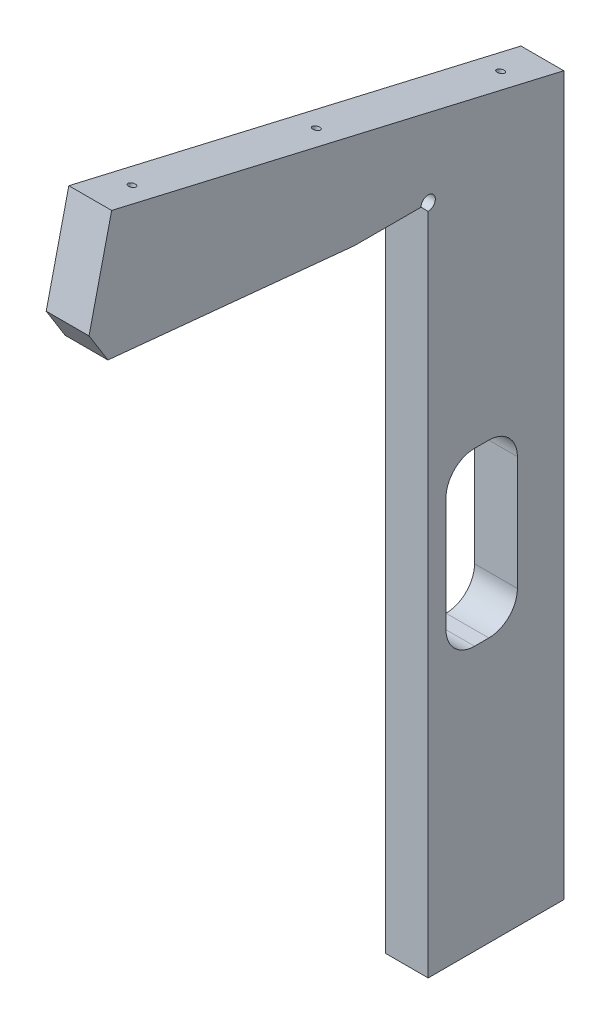
SolidWorks part; units mm, degrees
material "MDF"
ref_plane "Front Plane" through (0, 0, 0) normal (0, 0, 1) x (1, 0, 0)
ref_plane "Top Plane" through (0, 0, 0) normal (0, 1, 0) x (1, 0, 0)
ref_plane "Right Plane" through (0, 0, 0) normal (1, 0, 0) x (0, 0, -1)
sketch "Sketch2" plane through (-113.7888, 0, 0) normal (1, 0, 0) x (0, 0, -1)
  line L17 (0, 20.8246) -> (-83.8286, 40.3069)
  line L18 (0, 20.8246) -> (-83.8286, 40.3069)
  line L29 (-83.8286, 40.3069) -> (-93.1962, 0)
  line L30 (-83.8286, 40.3069) -> (-93.1962, 0)
  line L31 (-93.1962, 0) -> (-63.5, 0)
  line L32 (-93.1962, 0) -> (-63.5, 0)
  line L46 (0, -298.45) -> (-60.325, -298.45)
  line L47 (0, -392.9838) -> (0, -398.937) construction
  line L48 (-28.575, -298.45) -> (0, -298.45) construction
  line L53 (-8.8658, -437.642) -> (0, -437.642)
  line L55 (0, -437.642) -> (0, 20.8246)
  line L57 (-60.325, -3.175) -> (-60.325, -412.75)
  line L60 (0, -298.45) -> (0, 20.8246)
  line L62 (-60.325, -3.175) -> (-60.325, -298.45)
  arc A14 (-60.325, -3.175) -> (-63.5, 0) centre (-60.325, 0) ccw
  arc A15 (-60.325, -412.75) -> (-8.8658, -437.642) centre (-28.575, -412.75) ccw
  arc A17 (-60.325, -3.175) -> (-63.5, 0) centre (-60.325, 0) ccw
  dimension "D2" = 0
extrude "Boss-Extrude1" add sketch "Sketch2" along normal blind 19.05
sketch "Sketch3" plane through (-113.7888, 0, 0) normal (-1, 0, 0) x (0, 0, 1)
  line L0 (83.8286, 40.3069) -> (201.0857, 67.5582)
  line L1 (495.3358, 135.9439) -> (66.675, 36.3203) construction
  line L2 (201.0857, 67.5582) -> (214.0229, 11.8918)
  line L7 (83.8286, 40.3069) -> (93.1962, 0)
  line L8 (93.1962, 0) -> (214.0229, 11.8918)
  arc A0 (63.5, 0) -> (60.325, -3.175) centre (60.325, 0) ccw construction
  dimension "D1" = 57.15
  dimension "D2" = 152.4
extrude "Boss-Extrude2" add sketch "Sketch3" against normal through all
chamfer "Chamfer1" distance 12.7 angle 45 1 edges at (-104.2638, 11.8918, 214.0229) first distance on face at (-104.2638, 39.725, 207.5543)
hole_wizard "Hole3" positions "Sketch8" profile "Sketch9" legacy
sketch "Sketch8" plane through (0, 45.0826, -35.8775) normal (0, 0.974, -0.2264) x (-1, 0, 0)
  line L0 (218.5638, 29.4548) -> (218.5638, 115.5175) construction
  line L4 (202.6895, 537.9919) -> (202.6895, 97.9067) construction
  line L9 (88.3895, 537.9919) -> (88.3895, 97.9067) construction
  line L13 (104.2638, 29.4548) -> (104.2638, 235.8996) construction
  line L16 (0, 537.9919) -> (0, 29.4548) construction
  point P0 (218.5638, 102.8175)
  point P2 (218.5638, 48.5048)
  point P33 (202.6895, 123.3067)
  point P35 (202.6895, 317.9493)
  point P37 (202.6895, 518.9419)
  point P51 (88.3895, 518.9419)
  point P53 (88.3895, 317.9493)
  point P55 (88.3895, 123.3067)
  point P69 (104.2638, 216.8496)
  point P71 (104.2638, 132.6772)
  point P73 (104.2638, 48.5048)
  point P83 (-104.2638, 48.5048)
  point P84 (-104.2638, 132.6772)
  point P85 (-104.2638, 216.8496)
  point P86 (-88.3895, 123.3067)
  point P87 (-88.3895, 317.9493)
  point P88 (-88.3895, 518.9419)
  point P89 (-202.6895, 518.9419)
  point P90 (-202.6895, 317.9493)
  point P91 (-202.6895, 123.3067)
  point P92 (-218.5638, 48.5048)
  point P93 (-218.5638, 102.8175)
sketch "Sketch9" plane through (-218.5638, 68.3578, 64.2709) normal (1, 0, 0) x (0, 0.2264, 0.974)
  line L0 (0, 0) -> (0, 51.7539)
  line L1 (0, 51.7539) -> (1.5875, 50.8)
  line L2 (1.5875, 50.8) -> (1.5875, 4.0177)
  line L3 (1.5875, 4.0177) -> (5.08, 0)
  line L4 (5.08, 0) -> (0, 0)
  line L5 (0, -14.3089) -> (0, 102.4216) construction
  line L6 (0, 51.7539) -> (-1.5875, 50.8) construction
  line L7 (-1.5875, 4.0177) -> (-5.08, 0) construction
  dimension "Diameter" = 3.175
  dimension "Depth" = 50.8
  dimension "C-Sink Diameter" = 10.16
  dimension "C-Sink Angle" = 82
  dimension "Drill Angle" = 118
hole_wizard "Hole4" positions "Sketch10" profile "Sketch11" legacy
sketch "Sketch10" plane through (0, 0, -25.4) normal (0, 0, -1) x (-1, 0, 0)
  line L0 (218.5638, 0) -> (218.5638, -437.642) construction
  line L4 (104.2638, 0) -> (104.2638, -298.45) construction
  line L13 (120.1388, -460.375) -> (120.1388, -311.15) construction
  line L16 (126.4888, -311.15) -> (113.7888, -311.15) construction
  line L18 (126.4888, -304.8) -> (-126.4888, -304.8) construction
  line L22 (94.7388, -276.225) -> (-94.7388, -276.225) construction
  line L24 (-94.7388, -285.75) -> (-94.7388, -266.7) construction
  line L26 (94.7388, -285.75) -> (94.7388, -266.7) construction
  line L27 (-94.7388, 0) -> (-94.7388, -19.05) construction
  line L29 (94.7388, 0) -> (94.7388, -19.05) construction
  line L31 (94.7388, -9.525) -> (-94.7388, -9.525) construction
  point P15 (218.5638, -31.75)
  point P17 (218.5638, -218.821)
  point P19 (218.5638, -418.592)
  point P28 (104.2638, -19.05)
  point P30 (104.2638, -149.225)
  point P32 (104.2638, -279.4)
  point P69 (120.1388, -330.2)
  point P71 (120.1388, -441.325)
  point P76 (-120.1388, -441.325)
  point P77 (-120.1388, -330.2)
  point P80 (-104.2638, -279.4)
  point P81 (-104.2638, -149.225)
  point P82 (-104.2638, -19.05)
  point P83 (-218.5638, -418.592)
  point P84 (-218.5638, -218.821)
  point P85 (-218.5638, -31.75)
  point P99 (0, -304.8)
  point P101 (107.4388, -304.8)
  point P103 (-107.4388, -304.8)
  point P127 (75.6888, -276.225)
  point P129 (0, -276.225)
  point P131 (-75.6888, -276.225)
  point P152 (75.6888, -9.525)
  point P154 (0, -9.525)
  point P156 (-75.6888, -9.525)
sketch "Sketch11" plane through (75.6888, -9.525, -25.4) normal (1, 0, 0) x (0, 1, 0)
  line L0 (0, 0) -> (0, 39.0539)
  line L1 (0, 39.0539) -> (1.5875, 38.1)
  line L2 (1.5875, 38.1) -> (1.5875, 4.0177)
  line L3 (1.5875, 4.0177) -> (5.08, 0)
  line L4 (5.08, 0) -> (0, 0)
  line L5 (0, -14.3089) -> (0, 102.4216) construction
  line L6 (0, 39.0539) -> (-1.5875, 38.1) construction
  line L7 (-1.5875, 4.0177) -> (-5.08, 0) construction
  dimension "Diameter" = 3.175
  dimension "Depth" = 38.1
  dimension "C-Sink Diameter" = 10.16
  dimension "C-Sink Angle" = 82
  dimension "Drill Angle" = 118
sketch "Sketch12" plane through (-94.7388, 0, 0) normal (1, 0, 0) x (0, 0, -1)
  line L0 (-30.1625, -19.05) -> (-30.1625, -266.7) construction
  line L1 (-60.325, -19.05) -> (0, -19.05) construction
  line L2 (-60.325, -266.7) -> (0, -266.7) construction
  line L4 (-52.3875, -180.975) -> (-20.6375, -180.975)
  line L5 (-52.3875, -180.975) -> (-52.3875, -104.775)
  line L6 (-52.3875, -104.775) -> (-20.6375, -104.775)
  line L7 (-20.6375, -180.975) -> (-20.6375, -104.775)
  line L8 (-52.3875, -180.975) -> (-20.6375, -104.775) construction
  line L9 (-52.3875, -104.775) -> (-20.6375, -180.975) construction
  point P6 (-36.5125, -142.875)
  point P12 (-30.1625, -142.875)
  dimension "D1" = 31.75
  dimension "D2" = 76.2
  dimension "D3" = 6.35
extrude "Cut-Extrude1" cut sketch "Sketch12" against normal through all
fillet "Fillet1" radius 12.7 4 edges at (-104.2638, -180.975, 52.3875) (-104.2638, -104.775, 52.3875) (-104.2638, -180.975, 20.6375) (-104.2638, -104.775, 20.6375)
